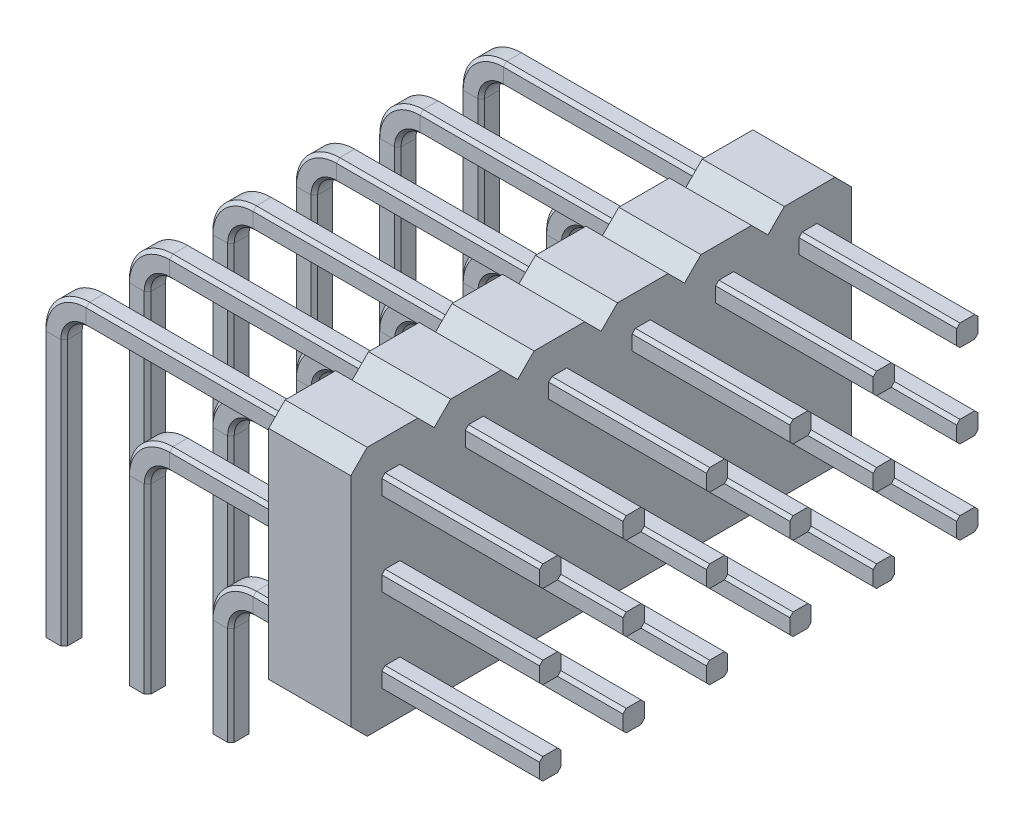
SolidWorks part; units mm, degrees
note: The reader was unsure of these and kept them because the rebuilt part matched: shared geometry of "Sketch1<3>", "Sketch2<3>", "Sketch1<4>", "Sketch2<4>".
ref_plane "Front Plane" through (0, 0, 0) normal (0, 0, 1) x (1, 0, 0)
ref_plane "Top Plane" through (0, 0, 0) normal (0, 1, 0) x (1, 0, 0)
ref_plane "Right Plane" through (0, 0, 0) normal (1, 0, 0) x (0, 0, -1)
sketch "Sketch1" plane through (0, 0, 0) normal (0, 1, 0) x (1, 0, 0)
  line L0 (-0.325, 0.225) -> (-0.225, 0.325)
  line L1 (-0.225, 0.325) -> (0.225, 0.325)
  line L2 (-0.325, 0.225) -> (-0.325, -0.225)
  line L3 (-0.225, -0.325) -> (0.225, -0.325)
  line L4 (0.325, 0.225) -> (0.325, -0.225)
  line L5 (-0.325, 0.325) -> (0.325, -0.325) construction
  line L6 (-0.325, -0.325) -> (0.325, 0.325) construction
  line L7 (0.225, 0.325) -> (0.325, 0.225)
  line L8 (0.225, -0.325) -> (0.325, -0.225)
  line L9 (-0.325, -0.225) -> (-0.225, -0.325)
  line L10 (2.315, -0.325) -> (2.765, -0.325)
  line L11 (2.215, -0.225) -> (2.315, -0.325)
  line L12 (2.215, 0.225) -> (2.215, -0.225)
  line L13 (2.215, 0.225) -> (2.315, 0.325)
  line L14 (2.315, 0.325) -> (2.765, 0.325)
  line L15 (2.765, 0.325) -> (2.865, 0.225)
  line L16 (2.865, 0.225) -> (2.865, -0.225)
  line L17 (2.765, -0.325) -> (2.865, -0.225)
  line L18 (4.855, -0.325) -> (5.305, -0.325)
  line L19 (4.755, -0.225) -> (4.855, -0.325)
  line L20 (4.755, 0.225) -> (4.755, -0.225)
  line L21 (4.755, 0.225) -> (4.855, 0.325)
  line L22 (4.855, 0.325) -> (5.305, 0.325)
  line L23 (5.305, 0.325) -> (5.405, 0.225)
  line L24 (5.405, 0.225) -> (5.405, -0.225)
  line L25 (5.305, -0.325) -> (5.405, -0.225)
  point P0 (0, 0)
  dimension "D1" = 0.65
  dimension "D2" = 3
sketch "Sketch2" plane through (0, 0, 0) normal (0, 0, 1) x (1, 0, 0)
  line L0 (0, 0) -> (0, 8.08)
  line L1 (1, 9.08) -> (14.8, 9.08)
  line L2 (2.54, 0) -> (2.54, 5.54)
  line L3 (2.315, 0) -> (2.765, 0) construction
  line L4 (3.54, 6.54) -> (14.8, 6.54)
  line L5 (5.08, 0) -> (5.08, 3)
  line L6 (4.855, 0) -> (5.305, 0) construction
  line L7 (6.08, 4) -> (14.8, 4)
  arc A0 (5.08, 3) -> (6.08, 4) centre (6.08, 3) cw
  arc A1 (2.54, 5.54) -> (3.54, 6.54) centre (3.54, 5.54) cw
  arc A2 (0, 8.08) -> (1, 9.08) centre (1, 8.08) cw
  point P16 (5.08, 4)
  point P19 (2.54, 6.54)
  point P22 (0, 9.08)
  dimension "D5" = 1
  dimension "D1" = 9.08
  dimension "D2" = 14.8
  dimension "D3" = 6.54
  dimension "D4" = 4
sweep "Sweep1" add profiles "Sketch1" path "Sketch2"
sweep "Sweep2" add profiles "Sketch1<3>" path "Sketch2<3>"
sketch "Sketch1<3>" plane through (0, 0, 0) normal (0, 1, 0) x (1, 0, 0) same geometry as "Sketch1"
sketch "Sketch2<3>" plane through (0, 0, 0) normal (0, 0, 1) x (1, 0, 0) same geometry as "Sketch2"
sweep "Sweep3" add profiles "Sketch1<4>" path "Sketch2<4>"
sketch "Sketch1<4>" plane through (0, 0, 0) normal (0, 1, 0) x (1, 0, 0) same geometry as "Sketch1"
sketch "Sketch2<4>" plane through (0, 0, 0) normal (0, 0, 1) x (1, 0, 0) same geometry as "Sketch2"
ref_plane "Plane1" through (7.5, 0, 0) normal (1, 0, 0) x (0, 0, -1)
sketch "Sketch5" plane through (7.5, 0, 0) normal (1, 0, 0) x (0, 0, -1)
  line L0 (0.325, 9.08) -> (0, 9.08) construction
  line L1 (-0.77, 10.35) -> (0.77, 10.35)
  line L2 (-1.27, 9.85) -> (-1.27, 3.23)
  line L3 (-0.77, 2.73) -> (0.77, 2.73)
  line L4 (1.27, 9.85) -> (1.27, 3.23)
  line L5 (-1.27, 10.35) -> (1.27, 2.73) construction
  line L6 (-1.27, 2.73) -> (1.27, 10.35) construction
  line L7 (0.325, 9.305) -> (0.325, 8.855) construction
  line L8 (-1.27, 9.85) -> (-0.77, 10.35)
  line L9 (0.77, 10.35) -> (1.27, 9.85)
  line L10 (0.77, 2.73) -> (1.27, 3.23)
  line L11 (-1.27, 3.23) -> (-0.77, 2.73)
  point P0 (0, 6.54)
  dimension "D1" = 7.62
  dimension "D2" = 2.54
extrude "Boss-Extrude1" add sketch "Sketch5" along normal blind 2.5
pattern_linear "LPattern1" count 6 spacing 2.54 along (0, 0, -1) of bodies 104
combine bodies "Combine1" operation type add bodies to combine 104 105 106 107 108 109
